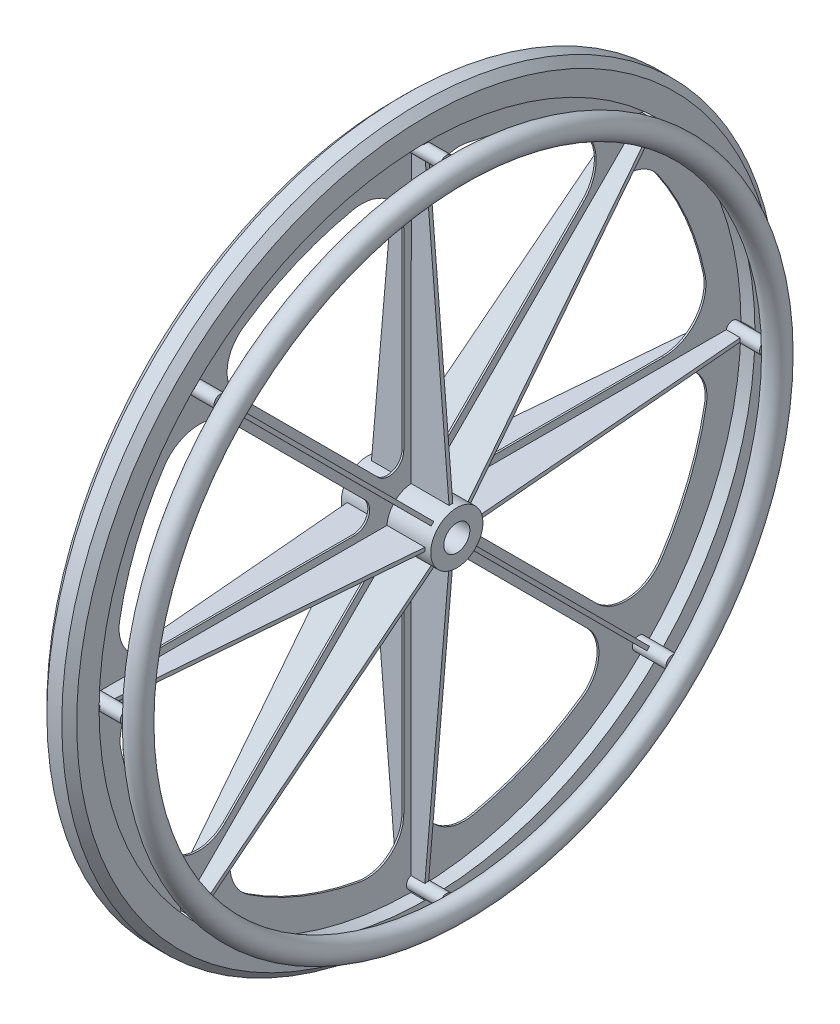
SolidWorks part; units mm, degrees
ref_plane "Front Plane" through (0, 0, 0) normal (0, 0, 1) x (1, 0, 0)
ref_plane "Top Plane" through (0, 0, 0) normal (0, 1, 0) x (1, 0, 0)
ref_plane "Right Plane" through (0, 0, 0) normal (1, 0, 0) x (0, 0, -1)
sketch "Sketch1" plane through (0, 0, 0) normal (1, 0, 0) x (0, 0, -1)
  circle A0 centre (0, 0) radius 22.225
  dimension "D1" = 44.45
extrude "Boss-Extrude1" add sketch "Sketch1" along normal blind 38.1 and the other way blind 38.1
sketch "Sketch2" plane through (0, 0, 0) normal (1, 0, 0) x (0, 0, -1)
  circle A0 centre (0, 0) radius 304.8
  dimension "D1" = 609.6
extrude "Boss-Extrude2" add sketch "Sketch2" along normal blind 0.762 and the other way blind 0.762 contours A0 | A0 region at (0, 0, 0)
sketch "Sketch4" plane through (0, 0, 0) normal (1, 0, 0) x (0, 0, -1)
  circle A0 centre (0, 0) radius 304.8 construction
  circle A1 centre (0, 0) radius 304.8
  circle A2 centre (0, 0) radius 279.4
  dimension "D1" = 25.4
extrude "Boss-Extrude3" add sketch "Sketch4" along normal blind 12.7 and the other way blind 12.7
sketch "Sketch5" plane through (0, 0, 0) normal (1, 0, 0) x (0, 0, -1)
  line L0 (0, 0) -> (0, 279.4) construction
  line L1 (0, 0) -> (197.5656, 197.5656) construction
  line L2 (7.87, 218.69) -> (7.87, 49.6604)
  line L3 (29.5503, 40.6801) -> (145.5218, 156.6517)
  circle A0 centre (0, 0) radius 279.4 construction
  circle A1 centre (0, 0) radius 279.4 construction
  circle A2 centre (0, 0) radius 304.8 construction
  circle A3 centre (0, 0) radius 304.8 construction
  arc A4 (139.9125, 211.9917) -> (45.28, 249.9314) centre (0, 0) ccw
  arc A5 (7.87, 49.6604) -> (29.5503, 40.6801) centre (20.57, 49.6604) ccw
  arc A6 (145.5218, 156.6517) -> (139.9125, 211.9917) centre (120.1402, 182.0333) ccw
  arc A7 (7.87, 218.69) -> (45.28, 249.9314) centre (39.62, 218.69) cw
  circle A8 centre (0, 0) radius 254 construction
  point P21 (0, 0)
  dimension "D6" = 12.7
  dimension "D7" = 31.75
  dimension "D1" = 45
  dimension "D3" = 164.0086
  dimension "D4" = 15.74
  dimension "D5" = 15.74
  dimension "D2" = 50.8
extrude "Cut-Extrude3" cut sketch "Sketch5" against normal through all and the other way through all
ref_plane "Plane1" through (0, 281.94, 0) normal (0, 1, 0) x (1, 0, 0)
sketch "Sketch6" plane through (0, 0, 0) normal (0, 1, 0) x (1, 0, 0)
  line L0 (38.1, -22.225) -> (38.1, 22.225) construction
  line L1 (-34.925, -1.6115) -> (34.925, -1.6115)
  line L2 (-34.925, -1.6115) -> (-34.925, 1.5635)
  line L3 (-34.925, 1.5635) -> (34.925, 1.5635)
  line L4 (34.925, -1.6115) -> (34.925, 1.5635)
  dimension "D1" = 69.85
  dimension "D2" = 3.175
  dimension "D3" = 3.175
sketch "Sketch7" plane through (0, 281.94, 0) normal (0, 1, 0) x (1, 0, 0)
  line L1 (11.3673, -1.4224) -> (-10.8577, -1.4224)
  line L2 (11.3673, -1.4224) -> (11.3673, 1.7526)
  line L3 (11.3673, 1.7526) -> (-10.8577, 1.7526)
  line L4 (-10.8577, -1.4224) -> (-10.8577, 1.7526)
  dimension "D1" = 22.225
  dimension "D2" = 3.175
loft "Loft2" add profiles "Sketch6", "Sketch7" connector at (-34.925, 0, 1.6115) connector at (-10.8577, 281.94, 1.4224)
sketch "Sketch8" plane through (0.762, 0, 0) normal (1, 0, 0) x (0, 0, -1)
  line L0 (0, 279.4) -> (0, 0) construction
  circle A0 centre (0, 0) radius 279.4 construction
  circle A1 centre (0, 272.265) radius 5.565
  dimension "D1" = 11.13
  dimension "D2" = 266.7
extrude "Boss-Extrude4" add sketch "Sketch8" along normal blind 28.575
pattern_circular "CirPattern1" count 8 over 360 about axis through (12.7, 0, 0) along (1, 0, 0) of "Boss-Extrude4", "Loft2", "Cut-Extrude3"
sketch "Sketch10" plane through (-38.1, 0, 0) normal (-1, 0, 0) x (0, 0, 1)
  circle A0 centre (0, 0) radius 11.1125
  dimension "D1" = 22.225
extrude "Cut-Extrude4" cut sketch "Sketch10" against normal through all
sketch "Sketch11" plane through (0, 0, 0) normal (0, 0, 1) x (1, 0, 0)
  line L0 (38.862, 272.2917) -> (-8.3929, 272.2917) construction
  line L1 (29.337, 266.7) -> (29.337, 277.83) construction
  line L2 (29.337, 277.83) -> (29.337, 272.2917) construction
  circle A0 centre (38.862, 272.2917) radius 9.525
  point P0 (29.337, 272.2917)
  point P9 (0, 0)
  point P10 (0, 0)
  point P11 (0, 0)
  point P12 (29.337, 272.265)
  point P13 (37.3309, 272.265)
  dimension "19.05mm" = 19.05
ref_axis "Axis1" through (-42.4243, 0, 0) along (1, 0, 0)
ref_axis "Axis2" through (52.7114, 0, 0) along (-1, 0, 0)
revolve "Revolve1" add sketch "Sketch11" angle 360 about axis through (-42.4243, 0, 0) along (1, 0, 0)
chamfer "Chamfer1" distance 6.35 angle 45 2 edges at (12.7, 0, -304.8) (-12.7, 0, -304.8)
